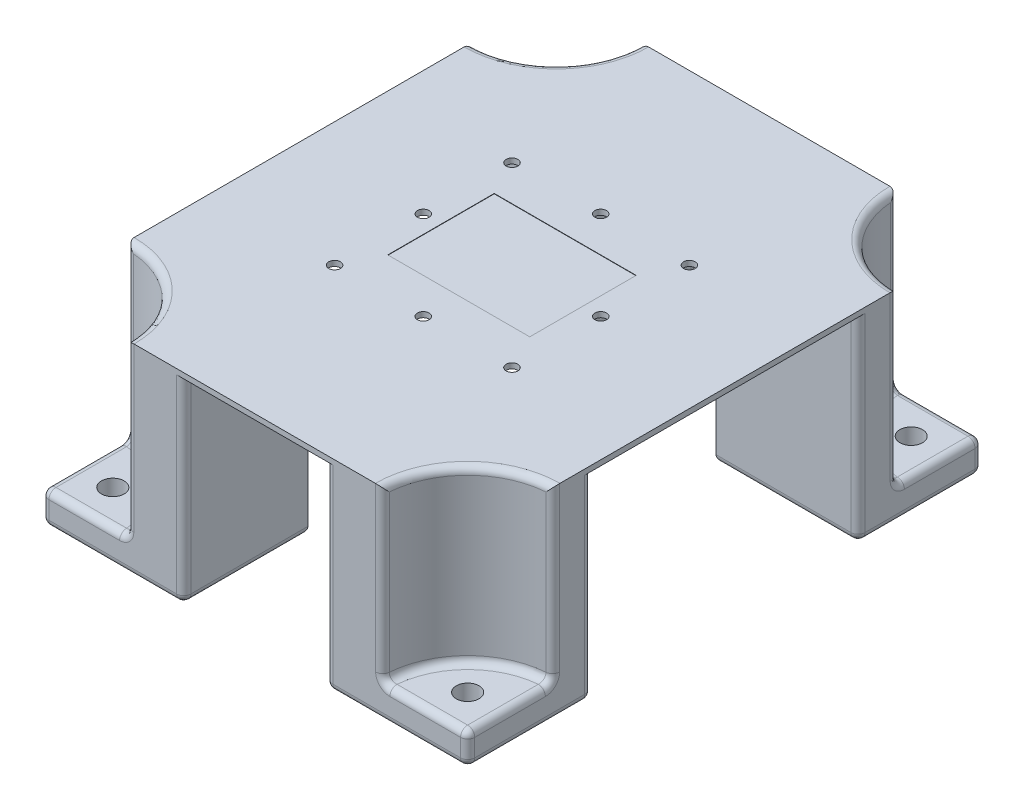
SolidWorks part; units mm, degrees
ref_plane "Front Plane" through (0, 0, 0) normal (0, 0, 1) x (1, 0, 0)
ref_plane "Top Plane" through (0, 0, 0) normal (0, 1, 0) x (1, 0, 0)
ref_plane "Right Plane" through (0, 0, 0) normal (1, 0, 0) x (0, 0, -1)
sketch "Sketch1" plane through (0, 0, 0) normal (0, 1, 0) x (1, 0, 0)
  line L0 (0, 0) -> (-153.2278, 0) construction
  line L1 (-60, -72.5) -> (60, -72.5) construction
  line L2 (-60, -72.5) -> (-60, 72.5) construction
  line L3 (-60, 72.5) -> (60, 72.5) construction
  line L4 (60, -72.5) -> (60, 72.5) construction
  line L5 (-60, -72.5) -> (60, 72.5) construction
  line L6 (-60, 72.5) -> (60, -72.5) construction
  line L7 (0, 0) -> (0, 50000) construction
  line L8 (-60, -72.5) -> (-20, -72.5)
  line L9 (60, -72.5) -> (20, -72.5)
  line L10 (60, -72.5) -> (60, -37.5)
  line L11 (60, -37.5) -> (20, -37.5)
  line L12 (20, -72.5) -> (20, -37.5)
  line L13 (-60, -72.5) -> (-60, -37.5)
  line L14 (-60, -37.5) -> (-20, -37.5)
  line L15 (-20, -72.5) -> (-20, -37.5)
  line L16 (-20, 72.5) -> (-20, 37.5)
  line L17 (-60, 37.5) -> (-20, 37.5)
  line L18 (-60, 72.5) -> (-60, 37.5)
  line L19 (20, 72.5) -> (20, 37.5)
  line L20 (60, 37.5) -> (20, 37.5)
  line L21 (60, 72.5) -> (60, 37.5)
  line L22 (60, 72.5) -> (20, 72.5)
  line L23 (-60, 72.5) -> (-20, 72.5)
  circle A0 centre (50, -62.5) radius 3.2 construction
  arc A1 (36, -72.5) -> (60, -48.5) centre (60, -72.5) cw construction
  point P0 (0, 0)
  dimension "D5" = 6.4
  dimension "D6" = 24
  dimension "D1" = 145
  dimension "D2" = 120
  dimension "D3" = 50
  dimension "D4" = 62.5
  dimension "D7" = 35
  dimension "D8" = 40
extrude "Boss-Extrude1" add sketch "Sketch1" along normal blind 55.5
sketch "Sketch2" plane through (0, 55.5, 0) normal (0, 1, 0) x (1, 0, 0)
  line L4 (-60, -37.5) -> (-60, -72.5)
  line L5 (-60, -72.5) -> (-20, -72.5)
  line L6 (-20, -72.5) -> (-20, -37.5)
  line L7 (-20, -37.5) -> (-60, -37.5)
  line L9 (-60, -72.5) -> (60, -72.5)
  line L12 (-20, 72.5) -> (-60, 72.5)
  line L13 (-60, 72.5) -> (-60, 37.5)
  line L14 (-60, 37.5) -> (-20, 37.5)
  line L15 (-20, 37.5) -> (-20, 72.5)
  line L17 (-60, 72.5) -> (-60, -72.5)
  line L20 (60, 72.5) -> (20, 72.5)
  line L21 (20, 72.5) -> (20, 37.5)
  line L22 (20, 37.5) -> (60, 37.5)
  line L23 (60, 37.5) -> (60, 72.5)
  line L24 (60, 72.5) -> (-60, 72.5)
  line L28 (60, -72.5) -> (60, -37.5)
  line L29 (60, -37.5) -> (20, -37.5)
  line L30 (20, -37.5) -> (20, -72.5)
  line L31 (20, -72.5) -> (60, -72.5)
  line L32 (60, -72.5) -> (60, 72.5)
  dimension "D1" = 0
  dimension "D2" = 0
  dimension "D3" = 0
  dimension "D4" = 0
extrude "Boss-Extrude2" add sketch "Sketch2" along normal blind 1.5
sketch "Sketch3" plane through (0, 57, 0) normal (0, 1, 0) x (1, 0, 0)
  line L0 (-60, -72.5) -> (60, -72.5) construction
  line L1 (60, -72.5) -> (60, 72.5) construction
  line L2 (0, 0) -> (84.5245, 0) construction
  line L3 (0, 0) -> (0, 44.5734) construction
  line L4 (-60, -48.5) -> (-60, -72.5)
  line L5 (36, -72.5) -> (60, -72.5)
  line L6 (-60, 72.5) -> (-60, -72.5)
  line L7 (-60, -72.5) -> (60, -72.5)
  line L8 (60, -72.5) -> (60, 72.5)
  line L9 (60, 72.5) -> (-60, 72.5)
  line L10 (-60, 72.5) -> (-60, 48.5)
  line L11 (-60, -72.5) -> (-36, -72.5)
  line L12 (60, -72.5) -> (60, -48.5)
  line L13 (60, 72.5) -> (36, 72.5)
  line L14 (60, 48.5) -> (60, 72.5)
  line L15 (-36, 72.5) -> (-60, 72.5)
  arc A0 (36, -72.5) -> (60, -48.5) centre (60, -72.5) cw
  arc A1 (-36, -72.5) -> (-60, -48.5) centre (-60, -72.5) ccw
  arc A2 (36, 72.5) -> (60, 48.5) centre (60, 72.5) ccw
  arc A3 (-36, 72.5) -> (-60, 48.5) centre (-60, 72.5) cw
  dimension "D2" = 24
  dimension "D1" = 0
extrude "Cut-Extrude1" cut sketch "Sketch3" against normal blind 48
sketch "Sketch4" plane through (0, 9, 0) normal (0, 1, 0) x (1, 0, 0)
  line L0 (0, 0) -> (-70.1979, 0) construction
  line L1 (0, 0) -> (0, 47.6209) construction
  circle A0 centre (50, -62.5) radius 3.2
  circle A1 centre (-50, -62.5) radius 3.2
  circle A2 centre (50, 62.5) radius 3.2
  circle A3 centre (-50, 62.5) radius 3.2
  dimension "D3" = 6.4
  dimension "D1" = 62.5
  dimension "D2" = 50
extrude "Cut-Extrude2" cut sketch "Sketch4" against normal up to surface (9 mm away) up to face at (-40, 0, 55)
fillet "Fillet1" radius 2 44 edges at (60, 9, 60.5) (48, 9, 72.5) (-48, 9, 72.5) (-60, 9, 60.5) (-60, 9, -60.5) (-48, 9, -72.5) (48, 9, -72.5) (60, 9, -60.5) (60, 33, 48.5) (43.0294, 9, 55.5294) (36, 33, 72.5) (43.0294, 57, 55.5294) (-36, 33, 72.5) (-43.0294, 9, 55.5294) (-60, 33, 48.5) (-43.0294, 57, 55.5294) (-60, 33, -48.5) (-43.0294, 9, -55.5294) (-36, 33, -72.5) (-43.0294, 57, -55.5294) (36, 33, -72.5) (43.0294, 9, -55.5294) (60, 33, -48.5) (43.0294, 57, -55.5294) (-60, 4.5, -72.5) (60, 4.5, -72.5) (-60, 4.5, 72.5) (60, 4.5, 72.5) (-40, 0, -72.5) (40, 0, -72.5) (-60, 0, -55) (20, 0, 55) (40, 0, 37.5) (60, 0, 55) (20, 0, -55) (-20, 0, -55) (60, 0, -55) (-40, 0, -37.5) (40, 0, -37.5) (40, 0, 72.5) (-40, 0, 72.5) (-20, 0, 55) (-40, 0, 37.5) (-60, 0, 55)
fillet "Fillet2" radius 2 16 edges at (-59.4142, 0.5858, 38.0858) (-59.4142, 0.5858, -38.0858) (20.5858, 0.5858, 71.9142) (-20.5858, 0.5858, 71.9142) (59.4142, 0.5858, -38.0858) (59.4142, 0.5858, 38.0858) (-20.5858, 0.5858, -71.9142) (20.5858, 0.5858, -71.9142) (-60, 28.75, 37.5) (-60, 28.75, -37.5) (20, 28.75, 72.5) (-20, 28.75, 72.5) (60, 28.75, -37.5) (60, 28.75, 37.5) (-20, 28.75, -72.5) (20, 28.75, -72.5)
sketch "Sketch5" plane through (0, 57, 0) normal (0, 1, 0) x (1, 0, 0)
  line L0 (0, 0) -> (-81.2621, 0) construction
  line L1 (0, 0) -> (0, 37.6033) construction
  circle A0 centre (25, -25) radius 1.65
  circle A1 centre (0, -25) radius 1.65
  circle A2 centre (-25, -25) radius 1.65
  circle A4 centre (-25, 0) radius 1.65
  circle A5 centre (0, 25) radius 1.65
  circle A6 centre (-25, 25) radius 1.65
  circle A7 centre (25, 0) radius 1.65
  circle A8 centre (25, 25) radius 1.65
  circle A9 centre (0, 0) radius 1.65 [skipped]
  dimension "D3" = 3.3
  dimension "D1" = 25
  dimension "D2" = 25
  dimension "D4" = 3
  dimension "D5" = 3
extrude "Cut-Extrude3" cut sketch "Sketch5" against normal up to surface (1.5 mm away) up to face at (0, 55.5, 0)
sketch "Sketch6" plane through (0, 57, 0) normal (0, 1, 0) x (1, 0, 0)
  line L0 (0, 0) -> (99.3535, 0) construction
  line L1 (0, 0) -> (0, -12.0882) construction
  line L3 (-20, 15) -> (20, 15)
  line L4 (-20, 15) -> (-20, -15)
  line L5 (-20, -15) -> (20, -15)
  line L6 (20, 15) -> (20, -15)
  line L7 (-20, 15) -> (20, -15) construction
  line L8 (-20, -15) -> (20, 15) construction
  point P3 (0, 0)
  dimension "D1" = 40
  dimension "D2" = 30
extrude "Cut-Extrude4" cut sketch "Sketch6" against normal blind 0.1
